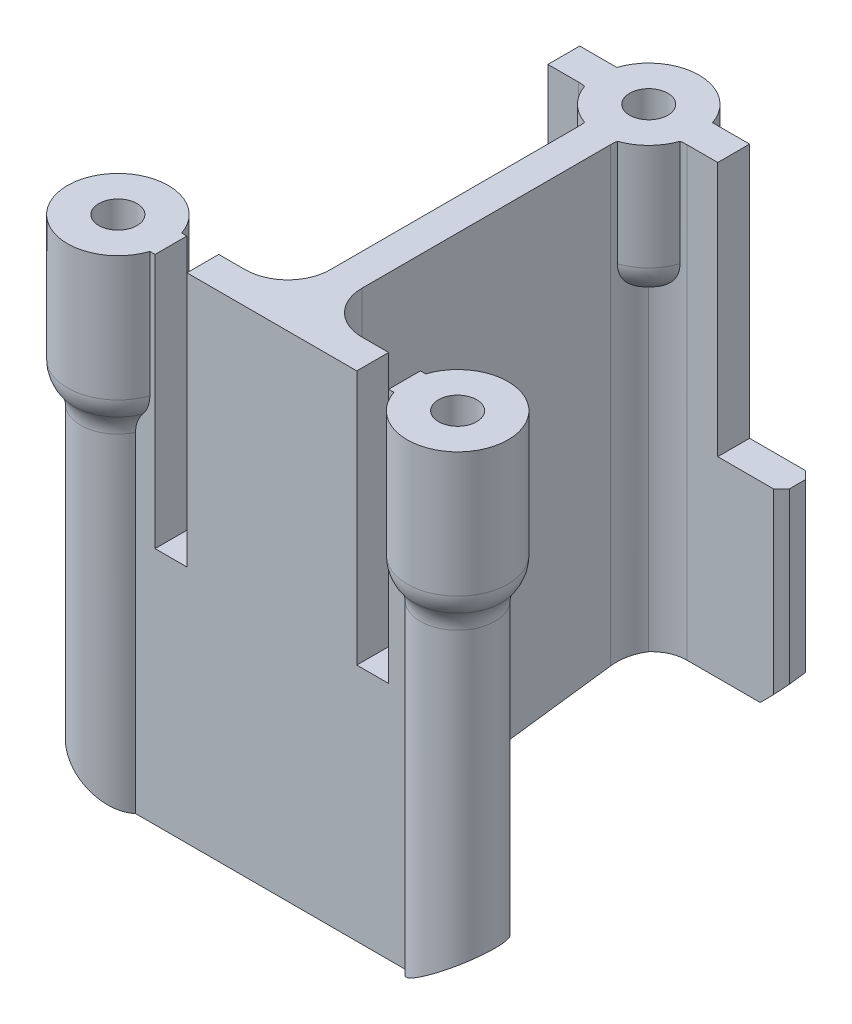
SolidWorks part; units mm, degrees
ref_plane "Front Plane" through (0, 0, 0) normal (0, 0, 1) x (1, 0, 0)
ref_plane "Top Plane" through (0, 0, 0) normal (0, 1, 0) x (1, 0, 0)
ref_plane "Right Plane" through (0, 0, 0) normal (1, 0, 0) x (0, 0, -1)
sketch "Sketch1" plane through (0, 0, 0) normal (0, 1, 0) x (1, 0, 0)
  line L0 (0, -1.5) -> (0, -24.4762) construction
  line L1 (-1.5, 1.5) -> (-1.5, -1.5) construction
  line L2 (-12.8377, 1.5) -> (-1.5, 1.5)
  line L3 (-12.8377, 1.5) -> (-12.8377, -1.5) construction
  line L4 (-12.8377, -1.5) -> (12.8377, -1.5)
  line L5 (12.8377, 1.5) -> (12.8377, -1.5) construction
  line L6 (-1.5, 30.8377) -> (1.5, 30.8377) construction
  line L7 (-1.5, 30.8377) -> (-1.5, 1.5)
  line L8 (-1.5, -1.5) -> (1.5, -1.5)
  line L9 (1.5, 30.8377) -> (1.5, 1.5)
  line L10 (0, 0) -> (0, -1.5) construction
  line L11 (1.5, 1.5) -> (1.5, -1.5) construction
  line L12 (-1.5, 1.5) -> (1.5, 1.5) construction
  line L13 (1.5, 1.5) -> (12.8377, 1.5)
  line L14 (-3.1623, 35.5) -> (3.1623, 35.5) construction
  line L15 (-14, 32.5) -> (-3.1623, 32.5)
  line L16 (-14, 32.5) -> (-14, 35.5)
  line L17 (-14, 35.5) -> (-3.1623, 35.5)
  line L18 (14, 32.5) -> (14, 35.5)
  line L19 (-14, 32.5) -> (-3.4801, 33.6271) construction
  line L20 (-14, 35.5) -> (-3.4801, 34.3729) construction
  line L21 (3.1623, 35.5) -> (14, 35.5)
  line L22 (-3.4801, 34.3729) -> (0, 34) construction
  line L23 (0, 34) -> (3.4801, 33.6271) construction
  line L24 (-3.4801, 33.6271) -> (0, 34) construction
  line L25 (3.4801, 34.3729) -> (14, 35.5) construction
  line L26 (-3.1623, 32.5) -> (3.1623, 32.5) construction
  line L27 (3.1623, 32.5) -> (14, 32.5)
  line L28 (0, 34) -> (3.4801, 34.3729) construction
  line L29 (3.4801, 33.6271) -> (14, 32.5) construction
  arc A0 (-12.8377, 1.5) -> (-12.8377, -1.5) centre (-16, 0) ccw
  arc A1 (12.8377, -1.5) -> (12.8377, 1.5) centre (16, 0) ccw
  arc A2 (1.5, 30.8377) -> (3.1623, 32.5) centre (0, 34) ccw
  arc A3 (12.8377, 1.5) -> (12.8377, -1.5) centre (16, 0) ccw construction
  arc A4 (-12.8377, -1.5) -> (-12.8377, 1.5) centre (-16, 0) ccw construction
  arc A5 (-1.5, 30.8377) -> (1.5, 30.8377) centre (0, 34) ccw construction
  arc A6 (3.4801, 33.6271) -> (3.4801, 34.3729) centre (0, 34) ccw construction
  arc A7 (3.1623, 35.5) -> (-3.1623, 35.5) centre (0, 34) ccw
  arc A8 (-3.4801, 34.3729) -> (-3.4801, 33.6271) centre (0, 34) ccw construction
  arc A9 (-3.1623, 32.5) -> (-1.5, 30.8377) centre (0, 34) ccw
  arc A10 (-3.1623, 35.5) -> (-3.4801, 34.3729) centre (0, 34) ccw construction
  arc A11 (3.4801, 34.3729) -> (3.1623, 35.5) centre (0, 34) ccw construction
  arc A12 (3.1623, 32.5) -> (3.4801, 33.6271) centre (0, 34) ccw construction
  arc A13 (-3.4801, 33.6271) -> (-3.1623, 32.5) centre (0, 34) ccw construction
  dimension "D1" = 7
  dimension "D8" = 3.5
  dimension "D2" = 16
  dimension "D3" = 34
  dimension "D4" = 3
  dimension "D5" = 3
  dimension "D6" = 3
  dimension "D7" = 28
extrude "Boss-Extrude1" add sketch "Sketch1" against normal blind 46.8 contours L9 A2 L7 L2 A0 L4 A1 L13 region at (0, 0, -14.2502)
sketch "Sketch3" plane through (0, 0, 0) normal (1, 0, 0) x (0, 0, -1)
  line L0 (-3.5, -46.8) -> (48.8194, -39.9027)
  line L1 (48.8194, -39.9027) -> (48.8194, -52.4526)
  line L2 (48.8194, -52.4526) -> (-3.5, -52.4526)
  line L3 (-3.5, -52.4526) -> (-3.5, -46.8)
  line L4 (-3.5, -46.8) -> (-3.5, -23.9782) construction
  line L5 (-3.5, 0) -> (-3.5, -46.8) construction
  dimension "D1" = 82.49
extrude "Cut-Extrude1" cut sketch "Sketch3" against normal through all both and the other way through all
sketch "Sketch4" plane through (0, 0, 0) normal (0, 1, 0) x (1, 0, 0)
  line L0 (0, -23.925) -> (0, 23.925) construction
  line L1 (-22.825, 0) -> (22.825, 0) construction
  circle A0 centre (0, 34) radius 5
  circle A1 centre (16, 0) radius 5
  circle A2 centre (-16, 0) radius 5
  arc A3 (-12.8377, 1.5) -> (-12.8377, -1.5) centre (-16, 0) ccw construction
  arc A4 (1.5, 30.8377) -> (3.1623, 32.5) centre (0, 34) ccw construction
  dimension "D1" = 10
extrude "Boss-Extrude2" [suppressed] add sketch "Sketch4" along normal blind 16.8
fillet "Fillet1" radius 4 6 edges at (1.5, -21.1366, -30.8377) (3.1623, -21.0271, -32.5) (-3.1623, -21.0271, -32.5) (-1.5, -21.1366, -30.8377) (-1.5, -23.0704, -1.5) (1.5, -23.0704, -1.5)
fillet "Fillet2" [suppressed] radius 4
fillet "Fillet3" [suppressed] radius 4
fillet "Fillet4" [suppressed] radius 4
chamfer "Chamfer1" distance 0.75 angle 45 4 edges at (-14, -21.0271, -32.5) (-14, -20.8293, -35.5) (14, -20.8293, -35.5) (14, -21.0271, -32.5)
sketch "Sketch5" plane through (0, 0, 0) normal (0, 1, 0) x (1, 0, 0)
  line L0 (-13.25, 35.5) -> (-3.1623, 35.5) construction
  line L1 (-11, 35.5) -> (-8, 35.5)
  line L2 (-11, 29.5378) -> (-11, -1.5)
  line L3 (-11, -1.5) -> (-8, -1.5)
  line L4 (-8, 35.5) -> (-8, -1.5)
  line L5 (-12.8377, -1.5) -> (12.8377, -1.5) construction
  line L6 (0, -23.925) -> (0, 23.925) construction
  line L7 (-11, 35.5) -> (-11, 29.5378) construction
  line L8 (-17.8995, 37.6377) -> (-11, 37.6377)
  line L9 (-17.8995, 37.6377) -> (-17.8995, 29.5378)
  line L10 (-17.8995, 29.5378) -> (-11, 29.5378)
  line L11 (-11, 37.6377) -> (-11, 35.5)
  line L12 (-11, 35.5) -> (-11, 29.5378) construction
  line L13 (11, 37.6377) -> (11, 35.5)
  line L14 (17.8995, 37.6377) -> (11, 37.6377)
  line L15 (17.8995, 37.6377) -> (17.8995, 29.5378)
  line L16 (17.8995, 29.5378) -> (11, 29.5378)
  line L17 (11, 29.5378) -> (11, -1.5)
  line L18 (11, -1.5) -> (8, -1.5)
  line L19 (8, 35.5) -> (8, -1.5)
  line L20 (11, 35.5) -> (8, 35.5)
  dimension "D1" = 3
  dimension "D2" = 8
extrude "Cut-Extrude2" cut sketch "Sketch5" against normal blind 24
sketch "Sketch6" plane through (0, 0, 0) normal (0, 1, 0) x (1, 0, 0)
  line L0 (0, -23.925) -> (0, 23.925) construction
  line L1 (-22.825, 0) -> (22.825, 0) construction
  circle A0 centre (0, 34) radius 4.75
  circle A1 centre (16, 0) radius 4.75
  circle A2 centre (-16, 0) radius 4.75
  arc A3 (-12.8377, 1.5) -> (-12.8377, -1.5) centre (-16, 0) ccw construction
  arc A4 (3.1623, 35.5) -> (-3.1623, 35.5) centre (0, 34) ccw construction
  arc A5 (12.8377, -1.5) -> (12.8377, 1.5) centre (16, 0) ccw construction
  dimension "D1" = 9.5
extrude "Boss-Extrude3" add sketch "Sketch6" against normal blind 13
hole_wizard "M3 Clearance Hole1" positions "Sketch8" profile "Sketch10" hole size "M3" standard "ANSI Metric"
sketch "Sketch8" plane through (0, 0, 0) normal (0, 1, 0) x (1, 0, 0)
  line L0 (0, -23.925) -> (0, 23.925) construction
  circle A0 centre (0, 34) radius 4.75 construction
  arc A2 (4.5069, 35.5) -> (-4.5069, 35.5) centre (0, 34) ccw construction
  point P0 (-16, 0)
  point P3 (16, 0)
  point P6 (0, 34)
sketch "Sketch10" plane through (-16, 0, 0) normal (1, 0, 0) x (0, 0, 1)
  line L0 (0, 0) -> (0, 13.5815)
  line L1 (0, 13.5815) -> (1.8, 12.5)
  line L2 (1.8, 12.5) -> (1.8, 0)
  line L5 (1.8, 0) -> (0, 0)
  line L10 (0, 13.5815) -> (-1.8, 12.5) construction
  line L11 (0, -6.35) -> (0, 107.95) construction
  dimension "Hole Dia." = 3.6
  dimension "Hole Depth" = 12.5
  dimension "Drill Angle" = 118
ref_plane "Plane1" through (0, -10, 0) normal (0, 1, 0) x (1, 0, 0)
sketch "Sketch11" plane through (0, -10, 0) normal (0, 1, 0) x (1, 0, 0)
  line L0 (0, -23.925) -> (0, 23.925) construction
  line L31 (-16, 3.7528) -> (-19.25, 1.8764) construction
  line L32 (-19.25, 1.8764) -> (-19.25, -1.8764)
  line L33 (-19.25, -1.8764) -> (-16, -3.7528)
  line L34 (-16, -3.7528) -> (-12.75, -1.8764)
  line L35 (-12.75, -1.8764) -> (-12.75, 1.8764)
  line L36 (-12.75, 1.8764) -> (-16, 3.7528) construction
  line L37 (16, 3.7528) -> (12.75, 1.8764) construction
  line L38 (12.75, 1.8764) -> (12.75, -1.8764)
  line L40 (12.75, -1.8764) -> (16, -3.7528)
  line L41 (16, -3.7528) -> (19.25, -1.8764)
  line L42 (19.25, -1.8764) -> (19.25, 1.8764)
  line L43 (19.25, 1.8764) -> (16, 3.7528) construction
  line L44 (0, 37.7528) -> (-3.25, 35.8764) construction
  line L45 (-3.25, 35.8764) -> (-3.25, 32.1236)
  line L46 (-3.25, 32.1236) -> (0, 30.2472)
  line L47 (0, 30.2472) -> (3.25, 32.1236)
  line L48 (3.25, 32.1236) -> (3.25, 35.8764)
  line L49 (3.25, 35.8764) -> (0, 37.7528) construction
  line L50 (-3.25, 35.8764) -> (-3.25, 39.9061)
  line L51 (-3.25, 39.9061) -> (3.25, 39.9061)
  line L52 (3.25, 39.9061) -> (3.25, 35.8764)
  line L53 (-19.25, 1.8764) -> (-19.25, 7.9963)
  line L54 (-19.25, 7.9963) -> (-12.75, 7.9963)
  line L55 (-12.75, 7.9963) -> (-12.75, 1.8764)
  line L56 (12.75, 1.8764) -> (12.75, 7.9963)
  line L57 (12.75, 7.9963) -> (19.25, 7.9963)
  line L58 (19.25, 7.9963) -> (19.25, 1.8764)
  circle A1 centre (-16, 0) radius 3.25 construction
  circle A5 centre (16, 0) radius 3.25 construction
  circle A6 centre (0, 34) radius 3.25 construction
  dimension "D1" = 6.5
extrude "Cut-Extrude3" cut sketch "Sketch11" along normal blind 3.5 contours L40 L41 | L48 L54 L46 L47 | L35 L33 L34 region at (-16, -10, -2.5773) region at (16, -10, -2.5773) region at (0, -10, -35.5289)
fillet "Fillet5" radius 3 3 edges at (19.5, -13, 0) (-19.5, -13, 0) (0, -13, -37.5)
fillet "Fillet6" radius 3 5 edges at (3.3588, -13, -30.6412) (-3.3588, -13, -30.6412) (0, -13, -38.75) (-20.75, -13, 0) (20.75, -13, 0)
sketch "Sketch12" plane through (0, 0, 1.5) normal (0, 0, 1) x (1, 0, 0)
  line L0 (-14, -46.5363) -> (-19.5, -21.5363)
  line L1 (12.8377, -46.5363) -> (-12.8377, -46.5363) construction
  line L2 (-19.5, -15.4367) -> (-19.5, -46.3386) construction
  line L3 (-19.5, -21.5363) -> (-31.9745, -21.5363)
  line L4 (-31.9745, -21.5363) -> (-31.9745, -49.8286)
  line L5 (-31.9745, -49.8286) -> (-14, -49.8286)
  line L6 (-14, -49.8286) -> (-14, -46.5363)
  line L7 (-11, -24) -> (-11, 0) construction
  dimension "D1" = 3
  dimension "D2" = 25
sketch "Sketch13" plane through (0, 0, 1.5) normal (0, 0, 1) x (1, 0, 0)
  line L0 (-12.8377, -46.5363) -> (-20.3603, -41.5363)
  line L1 (-20.3603, -41.5363) -> (-20.3603, -47.9492)
  line L2 (-20.3603, -47.9492) -> (-12.8377, -47.9492)
  line L3 (-12.8377, -47.9492) -> (-12.8377, -46.5363)
  line L4 (12.8377, -46.5363) -> (-12.8377, -46.5363) construction
  dimension "D1" = 5
extrude "Cut-Extrude5" cut sketch "Sketch13" against normal through all both and the other way through all
chamfer "Chamfer2" distance 2 angle 45 2 edges at (14, -41.8564, -34) (-14, -41.8564, -34)
mirror "Mirror1" about plane through (0, 0, 0) normal (1, 0, 0) of "Cut-Extrude5"
extrude "Cut-Extrude4" [suppressed] cut sketch "Sketch12" against normal through all both and the other way through all
